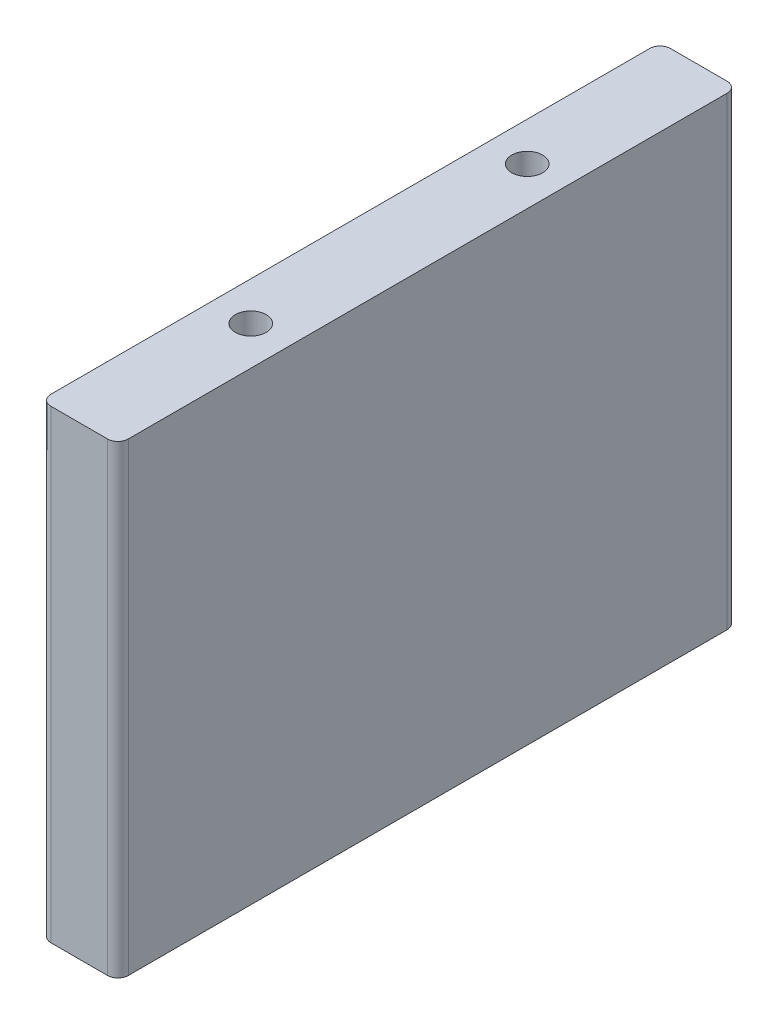
SolidWorks part; units mm, degrees
ref_plane "Front Plane" through (0, 0, 0) normal (0, 0, 1) x (1, 0, 0)
ref_plane "Top Plane" through (0, 0, 0) normal (0, 1, 0) x (1, 0, 0)
ref_plane "Right Plane" through (0, 0, 0) normal (1, 0, 0) x (0, 0, -1)
sketch "Sketch1" plane through (0, 0, 0) normal (0, 1, 0) x (1, 0, 0)
  line L1 (-4.7625, 38.1) -> (4.7625, 38.1)
  line L2 (-4.7625, 38.1) -> (-4.7625, -38.1)
  line L3 (-4.7625, -38.1) -> (4.7625, -38.1)
  line L4 (4.7625, 38.1) -> (4.7625, -38.1)
  point P4 (0, 38.1)
  point P6 (4.7625, 0)
  dimension "D1" = 9.525
  dimension "D2" = 76.2
extrude "Boss-Extrude1" add sketch "Sketch1" along normal mid plane 57.15
hole_wizard "#10-24 Tapped Hole1" positions "Sketch2" profile "Sketch3" tap size "#10-24" standard "ANSI Inch"
sketch "Sketch2" plane through (0, 28.575, 0) normal (0, 1, 0) x (1, 0, 0)
  point P0 (0, 17)
  point P2 (0, -17)
  point P6 (0, 0)
  dimension "D1" = 34
  dimension "D2" = 17
sketch "Sketch3" plane through (0, 28.575, -17) normal (1, 0, 0) x (0, 0, 1)
  line L0 (0, 0) -> (0, 20.1908)
  line L1 (0, 20.1908) -> (1.8986, 19.05)
  line L2 (1.8986, 19.05) -> (1.8986, 0)
  line L5 (1.8986, 0) -> (0, 0)
  line L10 (0, 20.1908) -> (-1.8987, 19.05) construction
  line L11 (0, -6.35) -> (0, 107.95) construction
  dimension "Tap Drill Dia." = 3.7973
  dimension "Tap Drill Depth" = 19.05
  dimension "Drill Angle" = 118
cosmetic thread "Hole Thread1" parameters "D1"=15.875, "D2"=4.826
cosmetic thread "Hole Thread2" parameters "D1"=15.875, "D2"=4.826
mirror "Mirror1" about plane through (0, 0, 0) normal (0, 1, 0) of "#10-24 Tapped Hole1"
cosmetic thread "Hole Thread3" parameters "D1"=15.875, "D2"=4.826
cosmetic thread "Hole Thread4" parameters "D1"=15.875, "D2"=4.826
fillet "Fillet1" radius 1.27 4 edges at (4.7625, 0, -38.1) (-4.7625, 0, -38.1) (4.7625, 0, 38.1) (-4.7625, 0, 38.1)
equation "\"D2@Sketch2\"=\"D1@Sketch2\"/2"
